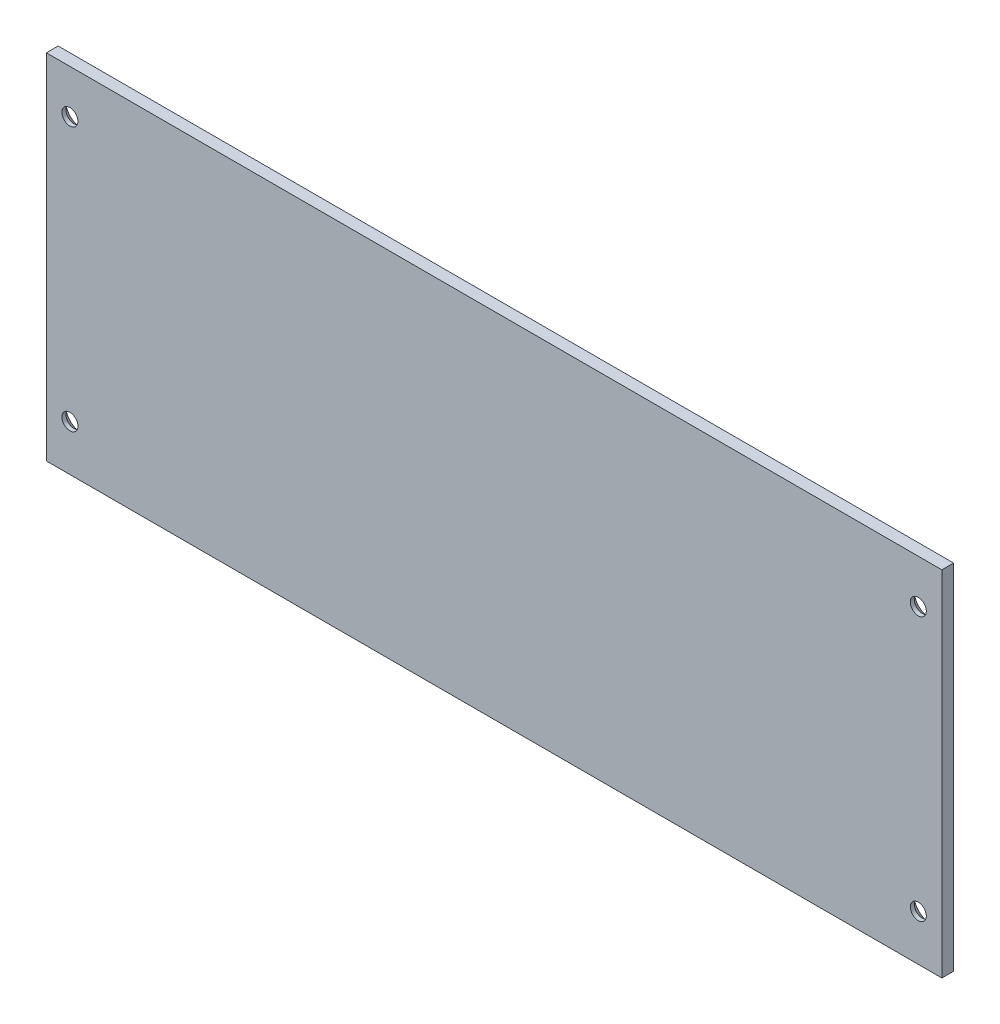
SolidWorks part; units mm, degrees
ref_plane "Alzado" through (0, 0, 0) normal (0, 0, 1) x (1, 0, 0)
ref_plane "Planta" through (0, 0, 0) normal (0, 1, 0) x (1, 0, 0)
ref_plane "Vista lateral" through (0, 0, 0) normal (1, 0, 0) x (0, 0, -1)
sketch "Sketch1" plane through (0, 0, 0) normal (0, 0, 1) x (1, 0, 0)
  line L1 (0, 0) -> (190, 0)
  line L2 (0, 0) -> (0, 75)
  line L3 (0, 75) -> (190, 75)
  line L4 (190, 0) -> (190, 75)
  dimension "D1" = 75
  dimension "190" = 190
extrude "Boss-Extrude1" add sketch "Sketch1" along normal blind 2.5
sketch "Sketch2" plane through (0, 0, 0) normal (0, 0, -1) x (-1, 0, 0)
  line L0 (-300.0838, 78.6125) -> (-85.5838, 78.6125) construction
  line L1 (0, 75) -> (0, 0) construction
  line L2 (2.1662, -2.259) -> (-192.8338, -2.259) construction
  line L4 (-190, 0) -> (-190, 75) construction
  circle A0 centre (-5, 65.7425) radius 1.585
  circle A1 centre (-5, 9.741) radius 1.585
  circle A2 centre (-185, 9.741) radius 1.585
  circle A3 centre (-185, 65.7425) radius 1.585
  point P0 (-5, 65.7425)
  point P6 (-5, 9.741)
  point P10 (-185, 9.741)
  point P14 (-185, 65.7425)
  dimension "D2" = 3.17
  dimension "D3" = 5
  dimension "D4" = 12
  dimension "D6" = 3.17
  dimension "D7" = 3.17
  dimension "D9" = 5
  dimension "D12" = 3.17
  dimension "D1" = 12.87
  dimension "D5" = 5
  dimension "D8" = 12
  dimension "D10" = 12.87
  dimension "D11" = 5
hole_wizard "Avellanado para tornillo con cabeza avellanada en cruz elevada de M31" positions "Sketch2" profile "Sketch3" countersink size "M3" standard "AS"
sketch "Sketch3" plane through (5, 65.7425, 0) normal (1, 0, 0) x (0, 1, 0)
  line L0 (0, 0) -> (0, 8.5215)
  line L1 (0, 8.5215) -> (1.7, 7.5)
  line L2 (1.7, 7.5) -> (1.7, 1.6417)
  line L3 (1.7, 1.6417) -> (3.4, 0)
  line L5 (3.4, 0) -> (0, 0)
  line L6 (-1.7, 1.6417) -> (-3.4, 0) construction
  line L10 (0, 8.5215) -> (-1.7, 7.5) construction
  line L11 (0, -6.35) -> (0, 107.95) construction
  dimension "Diámetro de taladro" = 3.4
  dimension "Profundidad de taladro" = 7.5
  dimension "Ángulo de avellanado cercano" = 6.8
  dimension "Ángulo de avellanado lejano" = 92
  dimension "Ángulo de perforador" = 118
equation "\"0.5.00mm\"=1"
